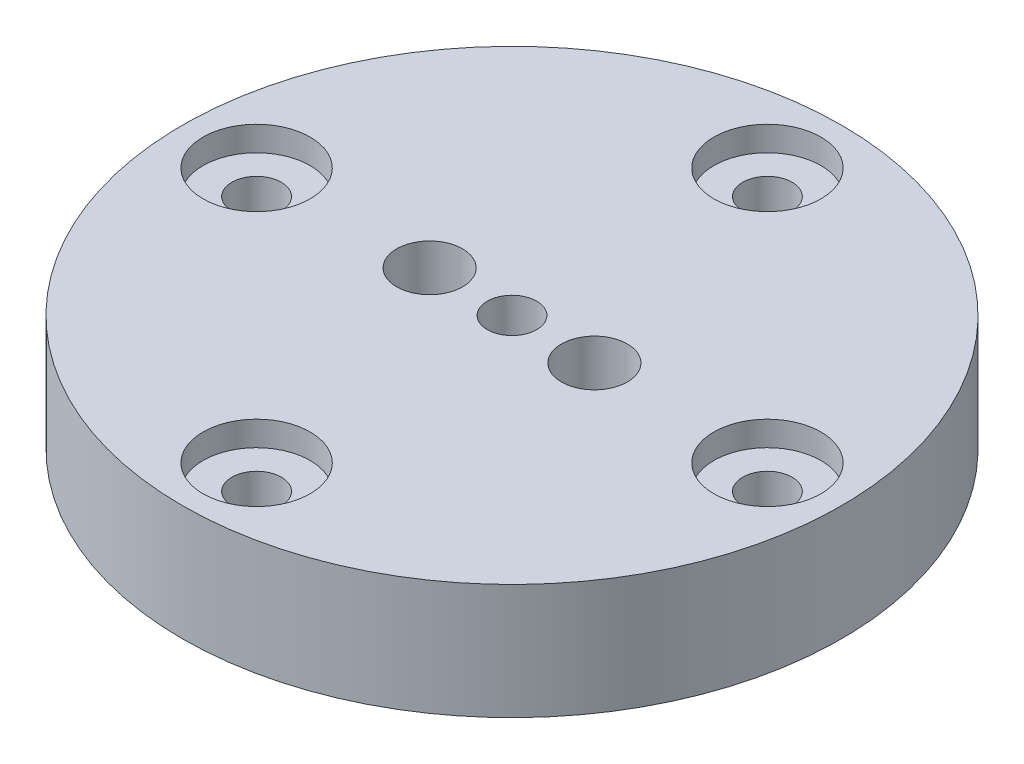
SolidWorks part; units mm, degrees
ref_plane "Front Plane" through (0, 0, 0) normal (0, 0, 1) x (1, 0, 0)
ref_plane "Top Plane" through (0, 0, 0) normal (0, 1, 0) x (1, 0, 0)
ref_plane "Right Plane" through (0, 0, 0) normal (1, 0, 0) x (0, 0, -1)
sketch "Sketch1" plane through (0, 0, 0) normal (0, 1, 0) x (1, 0, 0)
  circle A0 centre (0, 0) radius 15.5 construction
  circle A1 centre (0, 15.5) radius 1.5
  circle A2 centre (15.5, 0) radius 1.5
  circle A3 centre (0, -15.5) radius 1.5
  circle A4 centre (-15.5, 0) radius 1.5
  circle A5 centre (0, 0) radius 20
  circle A6 centre (0, 0) radius 5 construction
  circle A7 centre (-5, 0) radius 2
  circle A8 centre (5, 0) radius 2
  circle A9 centre (0, 0) radius 1.5
  point P14 (0, 0)
  dimension "D1" = 31
  dimension "D2" = 3
  dimension "D4" = 40
  dimension "D5" = 10
  dimension "D6" = 4
  dimension "D7" = 3
  dimension "D3" = 4
extrude "Boss-Extrude1" add sketch "Sketch1" along normal blind 7
sketch "Sketch2" plane through (0, 7, 0) normal (0, 1, 0) x (1, 0, 0)
  circle A0 centre (0, 0) radius 15.5 construction
  circle A1 centre (0, 15.5) radius 3.25
  circle A2 centre (15.5, 0) radius 3.25
  circle A3 centre (0, -15.5) radius 3.25
  circle A4 centre (-15.5, 0) radius 3.25
  point P15 (0, 0)
  dimension "D1" = 6.5
  dimension "D2" = 4
extrude "Cut-Extrude1" cut sketch "Sketch2" against normal blind 1.5
